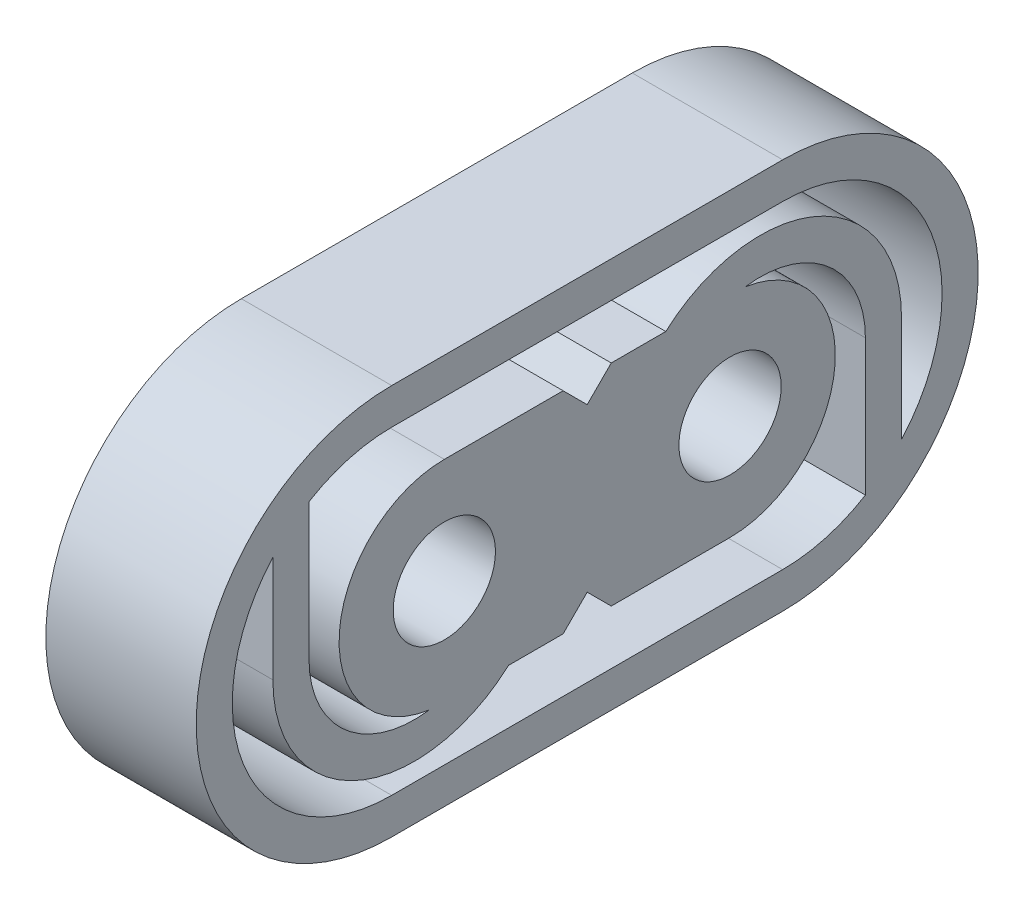
SolidWorks part; units mm, degrees
ref_plane "Front Plane" through (0, 0, 0) normal (1, 0, 0) x (0, 1, 0)
ref_plane "Top Plane" through (0, 0, 0) normal (0, 0, 1) x (0, 1, 0)
ref_plane "Right Plane" through (0, 0, 0) normal (0, 1, 0) x (-1, 0, 0)
sketch "Sketch2" plane through (0, 0, 0) normal (1, 0, 0) x (0, 1, 0)
  line L0 (-6.4721, 6.4962) -> (-6.4721, -6.5038)
  line L1 (-5.2721, 6.4962) -> (-5.2721, -6.5038)
  line L2 (0.0279, 10.4462) -> (3.5616, 10.4462)
  line L3 (4.5586, 9.2462) -> (0.0279, 9.2462)
  line L4 (-3.4721, 2.6094) -> (-3.4721, 0.7962)
  line L5 (-3.4721, 0.7962) -> (-2.6721, -0.0038)
  line L6 (-2.6721, -0.0038) -> (-3.4721, -0.8038)
  line L7 (-3.4721, -0.8038) -> (-3.4721, -4.7538)
  line L8 (3.5279, -2.6169) -> (3.5279, -0.8038)
  line L9 (3.5279, -0.8038) -> (2.7279, -0.0038)
  line L10 (2.7279, -0.0038) -> (3.5279, 0.7962)
  line L11 (3.5279, 0.7962) -> (3.5279, 4.7462)
  line L12 (5.3279, 6.4962) -> (5.3279, -6.5038)
  line L13 (6.5279, 6.4962) -> (6.5279, -6.5038)
  line L14 (-3.5059, -10.4538) -> (0.0279, -10.4538)
  line L15 (-4.5029, -9.2538) -> (0.0279, -9.2538)
  arc A0 (3.5279, 4.7462) -> (-3.4362, 5.2462) centre (0.0279, 4.7462) ccw
  arc A1 (0.0279, 10.4462) -> (-3.4721, 2.6094) centre (0.0279, 5.7462) ccw
  arc A2 (-6.4721, -6.5038) -> (6.5279, -6.5038) centre (0.0279, -6.5038) ccw
  arc A3 (-5.2721, -6.5038) -> (-4.5029, -9.2538) centre (0.0279, -6.5038) ccw
  arc A4 (5.3279, 6.4962) -> (4.5586, 9.2462) centre (0.0279, 6.4962) ccw
  arc A5 (6.5279, 6.4962) -> (-6.4721, 6.4962) centre (0.0279, 6.4962) ccw
  arc A6 (0.0279, -9.2538) -> (3.492, -5.2538) centre (0.0279, -5.7538) ccw
  arc A7 (0.0279, -10.4538) -> (3.5279, -2.6169) centre (0.0279, -5.7538) ccw
  arc A8 (-3.4721, -4.7538) -> (3.492, -5.2538) centre (0.0279, -4.7538) ccw
  arc A9 (0.0279, 9.2462) -> (-3.4362, 5.2462) centre (0.0279, 5.7462) ccw
  arc A10 (-3.5059, -10.4538) -> (5.3279, -6.5038) centre (0.0279, -6.5038) ccw
  arc A11 (3.5616, 10.4462) -> (-5.2721, 6.4962) centre (0.0279, 6.4962) ccw
  circle A12 centre (0.0279, 4.7462) radius 1.7
  circle A13 centre (0.0279, -4.7538) radius 1.7
extrude "Boss-Extrude2" add sketch "Sketch2" along normal blind 5
chamfer "Chamfer2" distance 1.8 angle 45 2 edges at (0, 0.0279, -6.4538) (0, 0.0279, 3.0462)
